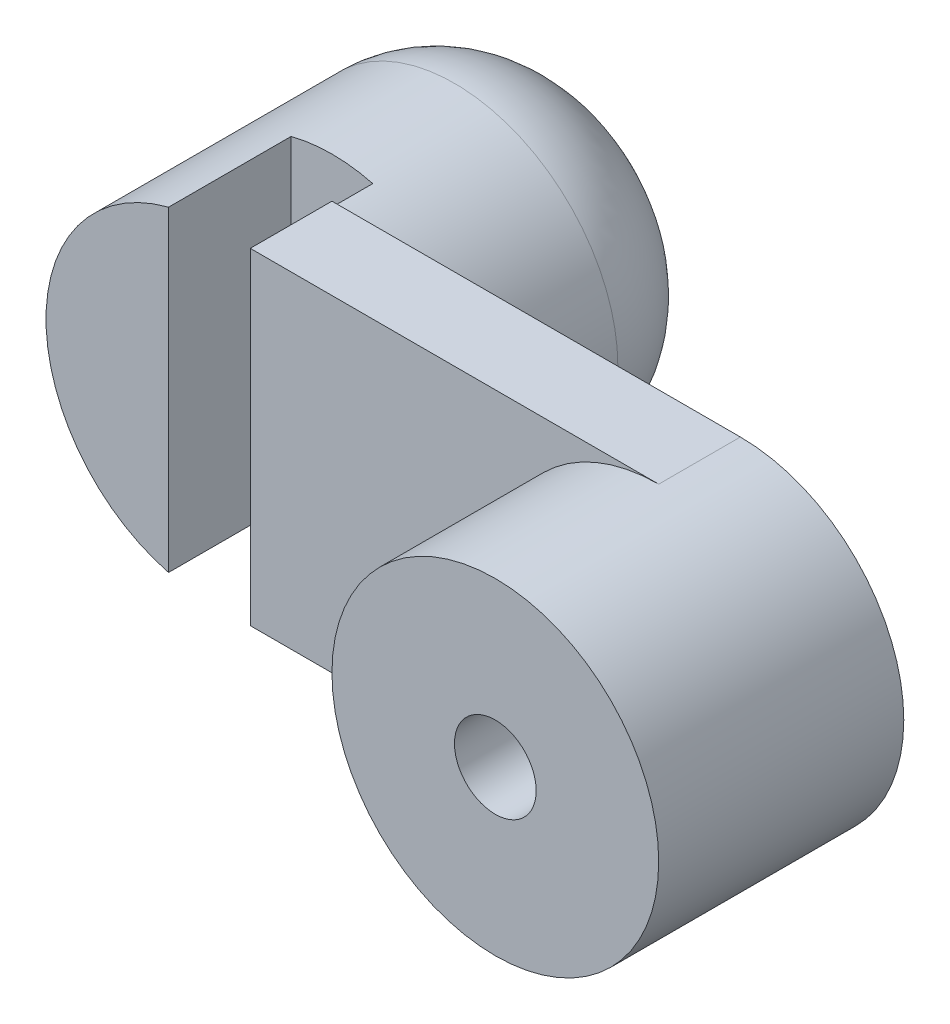
SolidWorks part; units mm, degrees
ref_plane "前视基准面" through (0, 0, 0) normal (0, 0, 1) x (1, 0, 0)
ref_plane "上视基准面" through (0, 0, 0) normal (0, 1, 0) x (1, 0, 0)
ref_plane "右视基准面" through (0, 0, 0) normal (1, 0, 0) x (0, 0, -1)
other "Configuration Table"
sketch "草图1" plane through (0, 0, 0) normal (0, 0, 1) x (1, 0, 0)
  circle A0 centre (0, 0) radius 2
  circle A1 centre (0, 0) radius 0.5
  dimension "D1" = 4
  dimension "D2" = 1
extrude "凸台-拉伸1" add sketch "草图1" along normal blind 4.5
fillet "圆角2" radius 1.5 1 edges at (2, 0, 0)
sketch "草图3" plane through (0, 0, 0) normal (0, 1, 0) x (1, 0, 0)
  line L0 (0, 0) -> (0, -3.5) construction
  line L1 (0, -3.5) -> (0, -4.5)
  line L2 (0, -3.5) -> (5.5, -3.5)
  line L3 (5.5, -3.5) -> (5.5, -4.5)
  line L4 (0, -4.5) -> (5.5, -4.5)
  dimension "D1" = 3.5
  dimension "D2" = 1
  dimension "D3" = 5.5
  dimension "D4" = 1
extrude "凸台-拉伸2" add sketch "草图3" along normal mid plane 4
sketch "草图4" plane through (0, 0, 3.5) normal (0, 0, -1) x (-1, 0, 0)
  line L0 (-5.5, 2) -> (-5.5, -2) construction
  circle A0 centre (-5.5, 0) radius 2
  circle A1 centre (-5.5, 0) radius 0.5
  dimension "D1" = 1
extrude "凸台-拉伸3" add sketch "草图4" against normal blind 1
sketch "草图5" plane through (0, 0, 3.5) normal (0, 0, -1) x (-1, 0, 0)
  line L0 (-5.5, 0.5) -> (-5.5, -0.5) construction
  circle A0 centre (-5.5, 0) radius 0.5
  dimension "D1" = 1
extrude "切除-拉伸2" cut sketch "草图5" against normal blind 4
sketch "草图6" plane through (0, 0, 4.5) normal (0, 0, 1) x (1, 0, 0)
  circle A0 centre (0, 0) radius 0.5
  dimension "D1" = 1
extrude "切除-拉伸3" cut sketch "草图6" against normal through all
sketch "草图2" plane through (0, 0, 4.5) normal (0, 0, 1) x (1, 0, 0)
  line L1 (-0.5, -2.0824) -> (0.5, -2.0824)
  line L2 (-0.5, -2.0824) -> (-0.5, 2.0824)
  line L3 (-0.5, 2.0824) -> (0.5, 2.0824)
  line L4 (0.5, -2.0824) -> (0.5, 2.0824)
  line L5 (-0.5, -2.0824) -> (0.5, 2.0824) construction
  line L6 (-0.5, 2.0824) -> (0.5, -2.0824) construction
  point P0 (0, 0)
  dimension "D1" = 1
extrude "切除-拉伸1" cut sketch "草图2" against normal blind 1.5
sketch "草图7" plane through (0, 0, 4.5) normal (0, 0, 1) x (1, 0, 0)
  circle A0 centre (5.5, 0) radius 0.5
  circle A1 centre (5.5, 0) radius 2
extrude "凸台-拉伸4" add sketch "草图7" along normal blind 2
